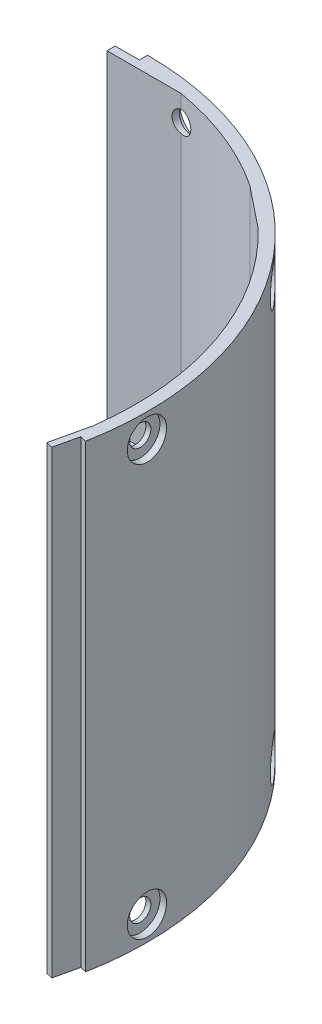
SolidWorks part; units mm, degrees
ref_plane "Спереди" through (0, 0, 0) normal (0, 0, 1) x (1, 0, 0)
ref_plane "Сверху" through (0, 0, 0) normal (0, 1, 0) x (1, 0, 0)
ref_plane "Справа" through (0, 0, 0) normal (1, 0, 0) x (0, 0, -1)
sketch "Эскиз2" plane through (0, 0, 0) normal (0, 1, 0) x (1, 0, 0)
  line L0 (0, -1000) -> (0, 49000) construction
  line L1 (-8.2529, 48.3) -> (8.2529, 48.3) construction
  line L2 (33.9524, 35.3303) -> (27.0476, 40.8587) construction
  line L3 (48.5627, -6.5315) -> (46.5973, -15.1557) construction
  line L4 (-4, 48.3) -> (8.2529, 48.3)
  line L5 (33.9524, 35.3303) -> (27.0476, 40.8587)
  line L6 (48.5627, -6.5315) -> (46.5973, -15.1557) construction
  line L7 (-4, 48.3) -> (-4, 49.65)
  line L8 (-4, 49.65) -> (0, 49.65)
  line L10 (-8.2529, 48.3) -> (-4, 48.3) construction
  line L12 (0, 0) -> (47.58, -10.8436) construction
  line L13 (50.1312, -9.3737) -> (49.0969, -9.138)
  line L14 (49.0969, -9.138) -> (48.2081, -13.038)
  line L15 (48.2081, -13.038) -> (47.1356, -12.7936)
  line L16 (47.58, -10.8436) -> (49.725, -11.3324) construction
  line L17 (47.1356, -12.7936) -> (48.5627, -6.5315)
  line L19 (0, 49.65) -> (0, 51)
  line L20 (0, 48.3) -> (0, 49.65) construction
  circle A0 centre (0, 0) radius 51 construction
  arc A1 (50.1312, -9.3737) -> (0, 51) centre (0, 0) ccw
  circle A2 centre (0, 0) radius 51 construction
  arc A3 (48.5627, -6.5315) -> (33.9524, 35.3303) centre (0, 0) ccw construction
  arc A4 (0, 51) -> (0, -51) centre (0, 0) ccw construction
  arc A5 (48.5627, -6.5315) -> (33.9524, 35.3303) centre (0, 0) ccw
  arc A6 (8.2529, 48.3) -> (27.0476, 40.8587) centre (0, 0) cw
  arc A7 (0, -51) -> (49.725, -11.3324) centre (0, 0) ccw construction
  arc A8 (49.725, -11.3324) -> (50.1312, -9.3737) centre (0, 0) ccw construction
  point P25 (48.6525, -11.088)
  dimension "D1" = 4
extrude "Бобышка-Вытянуть2" add sketch "Эскиз2" along normal up to surface (76 mm away)
ref_plane "Плоскость4" through (12.7171, 0, -36.1271) normal (-0.332, 0, 0.9433) x (0.9433, 0, 0.332)
sketch "Эскиз7" plane through (12.7171, 0, -36.1271) normal (-0.332, 0, 0.9433) x (0.9433, 0, 0.332)
  line L5 (-8.2529, 17) -> (5.2529, 17) construction
  line L6 (-8.2529, 17) -> (5.2529, 17) construction
  line L7 (8.2529, 14) -> (5.2529, 17) construction
  line L8 (8.2529, 14) -> (5.2529, 17)
  line L9 (-8.2529, 0) -> (8.2529, 0) construction
  line L16 (-8.2529, 0) -> (8.2529, 0)
  line L17 (-8.2529, 76) -> (-8.2529, 0) construction
  line L18 (-8.2529, 17) -> (-8.2529, 0) construction
  line L19 (8.7529, 14.2071) -> (8.7529, 0)
  line L20 (8.7529, 14.2071) -> (5.46, 17.5)
  line L21 (8.2529, 14) -> (8.2529, 0) construction
  line L22 (8.2529, 14) -> (8.2529, 0) construction
  line L23 (-8.7529, 17.5) -> (5.46, 17.5)
  line L24 (-8.7529, 17.5) -> (-8.7529, 0)
  line L25 (-8.7529, 0) -> (-8.2529, 0)
  line L26 (8.2529, 0) -> (8.7529, 0)
  dimension "D1" = 0.5
extrude "Вырез-Вытянуть3" cut sketch "Эскиз7" against normal through all contours L16 L26 L19 L20 L23 L24 L25 region at (12.587, 8.6121, -36.1729)
sketch "Эскиз9" plane through (0, 0, -48.3) normal (0, 0, 1) x (1, 0, 0)
  line L4 (8.7529, 0) -> (8.7529, 17.5)
  line L6 (-4, 76) -> (-4, 0) construction
  line L7 (-4, 19.5) -> (-4, 0)
  line L8 (-4, 76) -> (-4, 19.5) construction
  line L9 (-4, 19.5) -> (-6.5, 17) construction
  line L10 (-8.2529, 0) -> (-4, 0) construction
  line L11 (8.7529, 17.5) -> (6.7071, 17.5)
  line L12 (6.7071, 17.5) -> (3.7071, 20.5)
  line L13 (3.7071, 20.5) -> (-3.7071, 20.5)
  line L14 (-8.2529, 0) -> (8.2529, 0)
  line L15 (8.2529, 0) -> (8.2529, 17)
  line L24 (8.2529, 17) -> (6.5, 17)
  line L25 (6.5, 17) -> (3.5, 20)
  line L26 (3.5, 20) -> (-3.5, 20)
  line L28 (-3.7071, 20.5) -> (-4, 20.2071)
  line L29 (-3.5, 20) -> (-6.5, 17)
  line L30 (-6.5, 17) -> (-8.2529, 17)
  line L31 (-8.2529, 17) -> (-8.2529, 0)
  line L32 (-4, 0) -> (8.2529, 0)
  line L33 (8.2529, 0) -> (8.2529, 17) construction
  line L34 (8.2529, 17) -> (6.5, 17) construction
  line L35 (6.5, 17) -> (3.5, 20) construction
  line L36 (3.5, 20) -> (-3.5, 20) construction
  line L37 (-3.5, 20) -> (-4, 19.5)
  line L38 (-6.5, 17) -> (-8.2529, 17) construction
  line L39 (-8.2529, 17) -> (-8.2529, 0) construction
  line L40 (-4, 19.5) -> (-4, 20.2071)
  line L41 (-4, 20.2071) -> (-4.3536, 19.8536) construction
  line L42 (-3.7071, 20.5) -> (-4.3536, 19.8536) construction
  line L43 (8.7529, 0) -> (8.2529, 0)
  line M9 (-8.2529, 0) -> (8.2529, 0)
  line M10 (8.2529, 0) -> (8.2529, 17)
  line M11 (8.2529, 17) -> (6.5, 17)
  line M12 (6.5, 17) -> (3.5, 20)
  line M13 (3.5, 20) -> (-3.5, 20)
  line M14 (-3.5, 20) -> (-6.5, 17)
  dimension "D1" = 0
  dimension "D2" = 0.5
extrude "Вырез-Вытянуть4" cut sketch "Эскиз9" against normal through all contours L7 M14 M9 M10 M11 M12 M13 | L43 L4 L11 L12 L13 L28 L40 M14 M13 M12 M11 M10 region at (8.5029, 0.2414, -48.3) region at (1.9477, 9.6325, -48.3)
sketch "Эскиз10" plane through (0, 12, 0) normal (0, 1, 0) x (1, 0, 0)
  line L0 (-4, 48.3) -> (8.2529, 48.3) construction
  line L1 (-4, 48.3) -> (8.2529, 48.3)
  line L2 (23.8222, 42.8194) -> (20.9924, 43.8155) construction
  line L3 (8.2529, 48.3) -> (20.9924, 43.8155) construction
  line L4 (23.8222, 42.8194) -> (20.9924, 43.8155)
  line L5 (8.2529, 48.3) -> (20.9924, 43.8155)
  line L7 (23.4097, 41.9045) -> (20.6603, 42.8723)
  line L8 (8.082, 47.3) -> (20.6603, 42.8723)
  line L9 (-4, 47.3) -> (8.082, 47.3)
  line L10 (-4, 47.3) -> (-4, 48.3)
  line L11 (26.4956, 40.0248) -> (27.0476, 40.8587) construction
  line L12 (26.4956, 40.0248) -> (28.4646, 39.7241)
  line L13 (27.0476, 40.8587) -> (33.9524, 35.3303) construction
  line L14 (28.4646, 39.7241) -> (27.0476, 40.8587) construction
  line L15 (28.4646, 39.7241) -> (27.0476, 40.8587) construction
  line L16 (28.4646, 39.7241) -> (27.0476, 40.8587)
  arc A0 (27.0476, 40.8587) -> (8.2529, 48.3) centre (0, 0) ccw construction
  arc A1 (27.0476, 40.8587) -> (23.8222, 42.8194) centre (0, 0) ccw
  arc A2 (23.8222, 42.8194) -> (8.2529, 48.3) centre (0, 0) ccw construction
  arc A3 (26.4956, 40.0248) -> (23.4097, 41.9045) centre (0, 0) ccw
  dimension "D2" = 30
  dimension "D1" = 1
extrude "Бобышка-Вытянуть7" add sketch "Эскиз10" along normal blind 10
sketch "Эскиз13" plane through (0, 22, 0) normal (0, 1, 0) x (1, 0, 0)
  line L0 (23.8222, 42.8194) -> (8.2529, 48.3) construction
  line L1 (23.8222, 42.8194) -> (8.2529, 48.3)
  arc A0 (27.0476, 40.8587) -> (8.2529, 48.3) centre (0, 0) ccw construction
  arc A1 (27.0476, 40.8587) -> (8.2529, 48.3) centre (0, 0) ccw
  line M2 (23.8222, 42.8194) -> (8.2529, 48.3)
extrude "Бобышка-Вытянуть8" add sketch "Эскиз13" against normal up to surface (4.5 mm away) contours A1 M2 region at (16.1306, 22, -45.824) up to face at (13.0597, 17.5, -47.6707)
sketch "Эскиз14" plane through (0, 17.5, 0) normal (0, -1, 0) x (1, 0, 0)
  line L0 (21.3189, -44.1192) -> (21.1877, -43.7468)
  line L1 (21.1877, -43.7468) -> (8.2529, -48.3) construction
  line L4 (21.9869, -46.0171) -> (21.3189, -44.1192)
  line L5 (23.8222, -42.8194) -> (8.2529, -48.3)
  line L6 (8.2529, -48.3) -> (6.7071, -48.3)
  line L7 (6.7071, -48.3) -> (6.7071, -50.557)
  line L8 (21.9869, -46.0171) -> (21.3189, -44.1192)
  line L9 (23.8222, -42.8194) -> (21.1877, -43.7468)
  line L10 (8.2529, -48.3) -> (6.7071, -48.3) construction
  line L11 (6.7071, -48.3) -> (6.7071, -50.557) construction
  arc A2 (6.7071, -50.557) -> (21.9869, -46.0171) centre (0, 0) ccw
  arc A3 (21.3189, -44.1192) -> (23.8222, -42.8194) centre (0, 0) ccw
  arc A4 (6.7071, -50.557) -> (21.9869, -46.0171) centre (0, 0) ccw construction
  arc A5 (21.3189, -44.1192) -> (23.8222, -42.8194) centre (0, 0) ccw
  dimension "D1" = 0
extrude "Бобышка-Вытянуть9" add sketch "Эскиз14" along normal up to surface contours A5 L9 L0 up to face at (23.2708, 15.6229, -44.011)
chamfer "Фаска1" distance 1 angle 45 4 edges at (2.041, 22, -47.3) (15.7459, 22, -44.6022) (24.9703, 22, -40.9937) (27.4801, 22, -39.8745)
ref_plane "Плоскость5" through (51, 0, 0) normal (1, 0, 0) x (0, 0, -1)
sketch "Эскиз15" plane through (51, 0, 0) normal (1, 0, 0) x (0, 0, -1)
  line L0 (0, -1000) -> (0, 49000) construction
  circle A0 centre (0, 4) radius 3.25
  dimension "D1" = 6.5
  dimension "D2" = 4
extrude "Вырез-Вытянуть5" cut sketch "Эскиз15" against normal blind 1.2
sketch "Эскиз16" plane through (49.8, 0, 0) normal (1, 0, 0) x (0, 0, -1)
  circle A0 centre (0, 4) radius 3.25 construction
  circle A1 centre (0, 4) radius 3.25 construction
  circle A2 centre (0, 4) radius 1.75
  dimension "D1" = 3.5
extrude "Вырез-Вытянуть6" cut sketch "Эскиз16" against normal through all
pattern_circular "Круговой массив3" count 3 every 20 about axis through (0, 0, 0) along (0, 1, 0) skipping 1 of "Вырез-Вытянуть5", "Вырез-Вытянуть6"
sketch "Эскиз17" plane through (51, 0, 0) normal (1, 0, 0) x (0, 0, -1)
  line L0 (0, -1000) -> (0, 49000) construction
  line L1 (51, 76) -> (-9.3737, 76) construction
  circle A0 centre (0, 72) radius 3.25
  circle A1 centre (0, 4) radius 3.25 construction
  dimension "D1" = 4
extrude "Вырез-Вытянуть7" cut sketch "Эскиз17" against normal blind 1.2
sketch "Эскиз18" plane through (49.8, 0, 0) normal (1, 0, 0) x (0, 0, -1)
  circle A0 centre (0, 72) radius 3.25 construction
  circle A1 centre (0, 72) radius 3.25 construction
  circle A2 centre (0, 72) radius 1.75
  circle A3 centre (0, 4) radius 1.75 construction
extrude "Вырез-Вытянуть8" cut sketch "Эскиз18" against normal through all
pattern_circular "Круговой массив5" count 5 every 20 about axis through (0, 76, 0) along (0, 1, 0) skipping 1, 3 of "Вырез-Вытянуть8", "Вырез-Вытянуть7"
